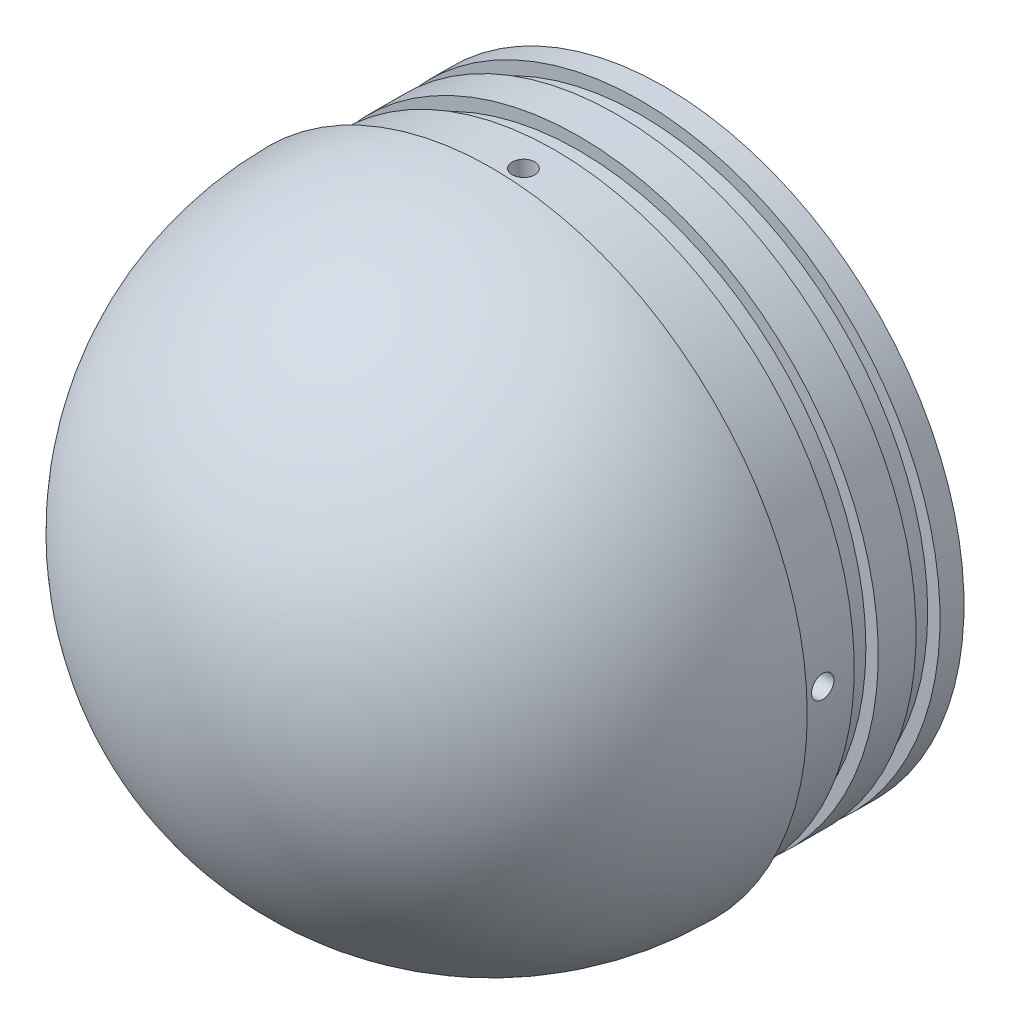
SolidWorks part; units mm, degrees
material "6061-T6 (SS)"
ref_plane "XY" through (0, 0, 0) normal (0, 0, 1) x (1, 0, 0)
ref_plane "XZ" through (0, 0, 0) normal (0, 1, 0) x (1, 0, 0)
ref_plane "YZ" through (0, 0, 0) normal (1, 0, 0) x (0, 0, -1)
ref_axis "X" through (-33.1508, 0, 0) along (1, 0, 0)
ref_axis "Y" through (0, -33.1508, 0) along (0, 1, 0)
ref_axis "Z" through (0, 0, 18.269) along (0, 0, -1)
sketch "Sketch2" plane through (0, 0, 0) normal (1, 0, 0) x (0, 0, -1)
  line L2 (-17.399, 30.1371) -> (-11.049, 30.1371)
  line L3 (-11.049, 30.1371) -> (-11.049, 28.8925)
  line L4 (-11.049, 28.8925) -> (-8.636, 28.8925)
  line L5 (-8.636, 28.8925) -> (-8.636, 30.1371)
  line L6 (-8.636, 30.1371) -> (-4.826, 30.1371)
  line L7 (-4.826, 30.1371) -> (-4.826, 28.8925)
  line L8 (-4.826, 28.8925) -> (-2.413, 28.8925)
  line L9 (-2.413, 28.8925) -> (-2.413, 30.1371)
  line L10 (-2.413, 30.1371) -> (0, 30.1371)
  line L11 (0, 30.1371) -> (0, 0)
  line L12 (0, 0) -> (-14.859, 0)
  line L13 (-17.399, 30.1371) -> (-17.399, 21.2471)
  line L14 (-17.399, 21.2471) -> (-14.859, 21.2471)
  line L15 (-14.859, 21.2471) -> (-14.859, 0)
  dimension "D1" = 30.1371
  dimension "D2" = 28.8925
  dimension "D3" = 2.413
  dimension "D4" = 3.81
  dimension "D5" = 2.413
  dimension "D6" = 8.89
  dimension "D7" = 6.35
  dimension "D8" = 2.54
revolve "Revolve1" add sketch "Sketch2" angle 360 about L12
hole_wizard "#4-40 Tapped Hole1" positions "3DSketch1" profile "Sketch3" tap size "#4-40" standard "ANSI Inch"
sketch3d "3DSketch1"
  line L0 (0, 0, 0) -> (0, 0, 14.224)
  line L1 (0, 0, 14.224) -> (-30.1371, 0, 14.224)
  line L3 (30.1371, 0, 14.224) -> (0, -30.1371, 14.224)
  line L5 (0, -30.1371, 14.224) -> (-30.1371, 0, 14.224)
  line L9 (0, 0, 14.224) -> (0, -30.1371, 14.224)
  line L11 (0, 0, 14.224) -> (30.1371, 0, 14.224)
  line L13 (0, 0, 14.224) -> (0, 30.1371, 14.224)
  line L15 (0, -30.1371, 11.049) -> (0, -30.1371, 17.399)
  line L16 (0, 30.1371, 14.224) -> (-30.1371, 0, 14.224)
  line L18 (30.1371, 0, 14.224) -> (0, 30.1371, 14.224)
  circle A1 centre (0, 0, 11.049) radius 30.1371 construction
  circle A2 centre (0, 0, 17.399) radius 30.1371 construction
  point P5 (0, -30.1371, 14.224)
  point P7 (30.1371, 0, 14.224)
  point P20 (-30.1371, 0, 14.224)
  point P1370 (0, 0, -19.0881)
  point P1373 (0, 0, -12.7381)
  point P1390 (0, 30.1371, 14.224)
cosmetic thread "Hole Thread2"
cosmetic thread "Hole Thread3"
cosmetic thread "Hole Thread5"
cosmetic thread "Hole Thread6"
sketch "Sketch3" plane through (0, -30.1371, 14.224) normal (1, 0, 0) x (0, 0, -1)
  line L0 (0, 0) -> (0, 8.2992)
  line L1 (0, 8.2992) -> (1.1303, 7.62)
  line L2 (1.1303, 7.62) -> (1.1303, 0)
  line L5 (1.1303, 0) -> (0, 0)
  line L10 (0, 8.2992) -> (-1.1303, 7.62) construction
  line L11 (0, -6.35) -> (0, 107.95) construction
  dimension "Tap Drill Dia." = 2.2606
  dimension "Tap Drill Depth" = 7.62
  dimension "Drill Angle" = 118
hole_wizard "Ø10.2 (10.2) Diameter Hole1" positions "Sketch4" profile "Sketch5" hole size "Ø10.2" standard "ANSI Metric" end condition through all
sketch "Sketch4" plane through (0, 0, 14.859) normal (0, 0, 1) x (1, 0, 0)
  point P0 (0, 0)
sketch "Sketch5" plane through (0, 0, 14.859) normal (1, 0, 0) x (0, -1, 0)
  line L0 (0, 0) -> (0, 14.859)
  line L1 (0, 14.859) -> (5.1, 14.859)
  line L2 (5.1, 14.859) -> (5.1, 0)
  line L5 (5.1, 0) -> (0, 0)
  line L11 (0, -6.35) -> (0, 107.95) construction
  dimension "Thru Hole Dia." = 10.2
  dimension "Thru Hole Depth" = 14.859
sketch "Sketch6" plane through (0, 0, 0) normal (0, 1, 0) x (1, 0, 0)
  line L0 (0, -17.399) -> (31.75, -17.399)
  line L1 (-21.2471, -17.399) -> (21.2471, -17.399) construction
  line L2 (0, -17.399) -> (0, -49.149)
  arc A0 (0, -49.149) -> (31.75, -17.399) centre (0, -17.399) ccw
  dimension "D1" = 31.75
revolve "Revolve2" add sketch "Sketch6" angle 360 about L2
